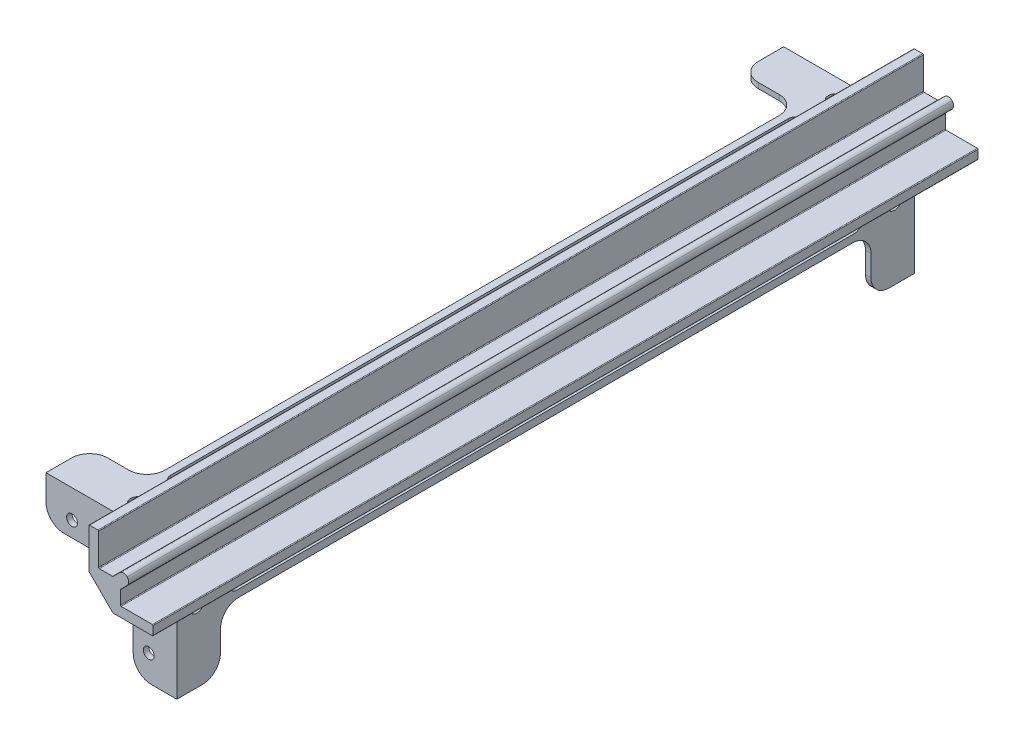
SolidWorks part; units mm, degrees
material "6061-T6 (SS)"
ref_plane "Front Plane" through (0, 0, 0) normal (0, 0, 1) x (1, 0, 0)
ref_plane "Top Plane" through (0, 0, 0) normal (0, 1, 0) x (1, 0, 0)
ref_plane "Right Plane" through (0, 0, 0) normal (1, 0, 0) x (0, 0, -1)
sketch "Sketch1" plane through (0, 0, 0) normal (0, 0, 1) x (1, 0, 0)
  line L0 (5.7105, 107.2306) -> (35.7105, 107.2306)
  line L5 (35.7105, 107.2306) -> (35.7105, 97.6946)
  line L8 (41.7105, 91.6946) -> (51.2465, 91.6946)
  line L9 (51.2465, 91.6946) -> (51.2465, 61.6946)
  line L26 (44.6218, 98.5558) -> (42.5718, 100.6058)
  line L36 (41.7105, 95.6446) -> (44.6218, 98.5558)
  line L37 (42.5718, 100.6058) -> (39.6605, 97.6946)
  line L38 (41.7105, 95.6446) -> (39.6605, 97.6946) construction
  line L39 (5.7105, 107.2306) -> (51.2465, 61.6946)
  line L46 (41.7105, 95.6446) -> (41.7105, 91.6946)
  line L47 (35.7105, 97.6946) -> (39.6605, 97.6946)
  point P44 (20.7124, 106.9061)
  dimension "D1" = 30
  dimension "D2" = 3.95
  dimension "D3" = 90
  dimension "D4" = 9.536
  dimension "D5" = 64.3976
extrude "Boss-Extrude1" add sketch "Sketch1" along normal blind 227
sketch "Sketch2" plane through (0, 0, 0) normal (0, 0, -1) x (-1, 0, 0)
  line L2 (-45.2465, 88.9946) -> (-45.2465, 80.9946)
  line L3 (-45.2465, 80.9946) -> (-43.7465, 80.9946)
  line L4 (-43.7465, 80.9946) -> (-43.7465, 88.9946)
  line L5 (-43.7465, 88.9946) -> (-39.6605, 88.9946)
  line L6 (-39.6605, 88.9946) -> (-33.0105, 95.6446)
  line L7 (-33.0105, 95.6446) -> (-33.0105, 99.7306)
  line L8 (-33.0105, 99.7306) -> (-25.0105, 99.7306)
  line L9 (-25.0105, 99.7306) -> (-25.0105, 101.2306)
  line L10 (-25.0105, 101.2306) -> (-33.0105, 101.2306)
  line L13 (27.2895, 108.6946) -> (-52.7105, 28.6946)
  line L16 (-51.2465, 61.6946) -> (-51.2465, 91.6946) construction
  line L17 (-35.7105, 107.2306) -> (-5.7105, 107.2306) construction
  line L19 (-52.7105, 92.6946) -> (-50.7105, 92.6946)
  line L20 (-50.7105, 92.6946) -> (-50.7105, 88.9946)
  line L21 (-50.7105, 88.9946) -> (-45.2465, 88.9946)
  line L22 (-52.7105, 92.6946) -> (-52.7105, 28.6946)
  line L23 (27.2895, 108.6946) -> (-36.7105, 108.6946)
  line L24 (-36.7105, 108.6946) -> (-36.7105, 106.6946)
  line L25 (-36.7105, 106.6946) -> (-33.0105, 106.6946)
  line L26 (-51.2465, 91.6946) -> (-41.7105, 91.6946) construction
  line L27 (-33.0105, 106.6946) -> (-33.0105, 101.2306)
  line L28 (-35.7105, 97.6946) -> (-35.7105, 107.2306) construction
  line L29 (-51.2465, 61.6946) -> (-51.2465, 91.6946) construction
  line L30 (-35.7105, 107.2306) -> (-5.7105, 107.2306) construction
  dimension "D2" = 2.7
  dimension "D3" = 2.7
  dimension "D4" = 64
  dimension "D5" = 1.5
  dimension "D6" = 8
  dimension "D7" = 1.5
  dimension "D8" = 8
  dimension "D9" = 6
  dimension "D10" = 6
  dimension "D11" = 0.536
  dimension "D12" = 0.536
  dimension "D13" = 2
  dimension "D14" = 2
  dimension "D15" = 1
  dimension "D16" = 1
extrude "Cut-Extrude1" cut sketch "Sketch2" against normal through all
sketch "Sketch3" plane through (0, 101.2306, 0) normal (0, 1, 0) x (1, 0, 0)
  line L1 (33.0105, -13.5) -> (23.0105, -13.5)
  line L2 (33.0105, -13.5) -> (33.0105, 2)
  line L3 (33.0105, 2) -> (23.0105, 2)
  line L4 (23.0105, -13.5) -> (23.0105, 2)
  line L5 (33.0105, -227) -> (25.0105, -227) construction
  line L6 (33.0105, -213.5) -> (23.0105, -213.5)
  line L7 (33.0105, -213.5) -> (33.0105, -229)
  line L8 (33.0105, -229) -> (23.0105, -229)
  line L9 (23.0105, -213.5) -> (23.0105, -229)
  line L14 (33.0105, 0) -> (25.0105, 0) construction
  line L15 (25.0105, -227) -> (25.0105, 0) construction
  line L16 (29.0105, -28.5) -> (29.0105, -198.5) construction
  line L17 (31.0105, -28.5) -> (31.0105, -198.5)
  line L18 (27.0105, -28.5) -> (27.0105, -198.5)
  arc A0 (31.0105, -28.5) -> (27.0105, -28.5) centre (29.0105, -28.5) ccw
  arc A1 (27.0105, -198.5) -> (31.0105, -198.5) centre (29.0105, -198.5) ccw
  point P22 (29.0105, -113.5)
  dimension "D8" = 2
  dimension "D1" = 13.5
  dimension "D2" = 13.5
  dimension "D3" = 2
  dimension "D4" = 15
  dimension "D6" = 2
  dimension "D7" = 2
  dimension "D9" = 4
  dimension "D10" = 15
extrude "Cut-Extrude2" cut sketch "Sketch3" against normal through all
sketch "Sketch4" plane through (45.2465, 0, 0) normal (1, 0, 0) x (0, 0, -1)
  line L1 (-213.5, 88.9946) -> (-229, 88.9946)
  line L2 (-213.5, 88.9946) -> (-213.5, 78.9946)
  line L3 (-213.5, 78.9946) -> (-229, 78.9946)
  line L4 (-229, 88.9946) -> (-229, 78.9946)
  line L5 (-227, 80.9946) -> (0, 80.9946) construction
  line L6 (-13.5, 88.9946) -> (2, 88.9946)
  line L7 (-13.5, 88.9946) -> (-13.5, 78.9946)
  line L8 (-13.5, 78.9946) -> (2, 78.9946)
  line L9 (2, 88.9946) -> (2, 78.9946)
  line L14 (0, 80.9946) -> (0, 88.9946) construction
  line L15 (-227, 80.9946) -> (-227, 88.9946) construction
  line L16 (-198.5, 84.9946) -> (-28.5, 84.9946) construction
  line L17 (-198.5, 86.9946) -> (-28.5, 86.9946)
  line L18 (-198.5, 82.9946) -> (-28.5, 82.9946)
  arc A0 (-198.5, 86.9946) -> (-198.5, 82.9946) centre (-198.5, 84.9946) ccw
  arc A1 (-28.5, 82.9946) -> (-28.5, 86.9946) centre (-28.5, 84.9946) ccw
  point P22 (-113.5, 84.9946)
  point P27 (-213.5, 83.9946)
  dimension "D9" = 2
  dimension "D1" = 2
  dimension "D2" = 2
  dimension "D3" = 2
  dimension "D4" = 13.5
  dimension "D5" = 13.5
  dimension "D6" = 2
  dimension "D7" = 15
  dimension "D8" = 4
  dimension "D10" = 15
extrude "Cut-Extrude3" cut sketch "Sketch4" against normal through all
fillet "Fillet3" radius 1.5 2 edges at (44.6218, 98.5558, 113.5) (42.5718, 100.6058, 113.5)
sketch "Sketch6" plane through (0, 0, 13.5) normal (0, 0, -1) x (-1, 0, 0)
  line L8 (-45.2465, 90.1946) -> (-45.2465, 65.2306)
  line L9 (-45.2465, 65.2306) -> (-33.2465, 65.2306)
  line L10 (-33.2465, 65.2306) -> (-33.2465, 89.2306)
  line L11 (-9.2465, 101.2306) -> (-34.2105, 101.2306)
  line L12 (-9.2465, 101.2306) -> (-9.2465, 89.2306)
  line L13 (-9.2465, 89.2306) -> (-33.2465, 89.2306)
  line L14 (-33.0105, 101.2306) -> (-25.0105, 101.2306) construction
  line L15 (-45.2465, 88.9946) -> (-45.2465, 80.9946) construction
  line L16 (-34.2105, 101.2306) -> (-34.2105, 96.2306)
  line L17 (-34.2105, 96.2306) -> (-40.2465, 90.1946)
  line L18 (-40.2465, 90.1946) -> (-45.2465, 90.1946)
  line L19 (-50.7105, 91.6946) -> (-41.7105, 91.6946) construction
  line L20 (-35.7105, 97.6946) -> (-35.7105, 106.6946) construction
  dimension "D1" = 12
  dimension "D2" = 24
  dimension "D3" = 1.5
  dimension "D4" = 1.5
  dimension "D5" = 5
extrude "Boss-Extrude3" add sketch "Sketch6" along normal blind 1.5
sketch "Sketch7" plane through (0, 0, 213.5) normal (0, 0, 1) x (1, 0, 0)
  line L0 (9.2465, 101.2306) -> (34.2105, 101.2306)
  line L1 (34.2105, 101.2306) -> (34.2105, 96.2306)
  line L2 (34.2105, 96.2306) -> (40.2465, 90.1946)
  line L3 (45.2465, 65.2306) -> (45.2465, 90.1946)
  line L4 (45.2465, 90.1946) -> (40.2465, 90.1946)
  line L5 (45.2465, 65.2306) -> (33.2465, 65.2306)
  line L6 (33.2465, 65.2306) -> (33.2465, 89.2306)
  line L7 (33.2465, 89.2306) -> (9.2465, 89.2306)
  line L8 (9.2465, 89.2306) -> (9.2465, 101.2306)
  line L9 (35.7105, 97.6946) -> (35.7105, 106.6946) construction
  line L10 (50.7105, 91.6946) -> (41.7105, 91.6946) construction
  dimension "D1" = 1.5
  dimension "D2" = 1.5
  dimension "D3" = 5
  dimension "D4" = 12
extrude "Boss-Extrude4" add sketch "Sketch7" along normal blind 1.5
sketch "Sketch9" plane through (0, 101.2306, 0) normal (0, 1, 0) x (1, 0, 0)
  line L0 (35.2465, -215) -> (9.2465, -215)
  line L1 (9.2465, -215) -> (9.2465, -203)
  line L2 (9.2465, -203) -> (35.2465, -203)
  line L3 (35.2465, -203) -> (35.2465, -215)
  line L4 (35.2465, -12) -> (9.2465, -12)
  line L5 (9.2465, -12) -> (9.2465, -24)
  line L6 (9.2465, -24) -> (35.2465, -24)
  line L7 (35.2465, -24) -> (35.2465, -12)
  dimension "D1" = 12
  dimension "D2" = 26
extrude "Boss-Extrude5" add sketch "Sketch9" against normal blind 1.5
sketch "Sketch10" plane through (45.2465, 0, 0) normal (1, 0, 0) x (0, 0, -1)
  line L0 (-215, 65.2306) -> (-215, 91.2306)
  line L1 (-215, 91.2306) -> (-203, 91.2306)
  line L2 (-203, 91.2306) -> (-203, 65.2306)
  line L3 (-203, 65.2306) -> (-215, 65.2306)
  line L4 (-12, 65.2306) -> (-12, 91.2306)
  line L5 (-12, 91.2306) -> (-24, 91.2306)
  line L6 (-24, 91.2306) -> (-24, 65.2306)
  line L7 (-24, 65.2306) -> (-12, 65.2306)
  dimension "D1" = 12
  dimension "D2" = 26
extrude "Boss-Extrude6" add sketch "Sketch10" against normal blind 1.5
fillet "Fillet7" radius 5 14 edges at (9.2465, 100.4806, 24) (9.2465, 89.2306, 12.75) (33.2465, 89.2306, 12.75) (33.2465, 65.2306, 12.75) (44.4965, 65.2306, 24) (44.4965, 80.9946, 24) (25.0105, 100.4806, 24) (44.4965, 80.9946, 203) (25.0105, 100.4806, 203) (9.2465, 100.4806, 203) (44.4965, 65.2306, 203) (33.2465, 65.2306, 214.25) (9.2465, 89.2306, 214.25) (33.2465, 89.2306, 214.25)
sketch "Sketch11" plane through (45.2465, 0, 0) normal (1, 0, 0) x (0, 0, -1)
  line L1 (-215, 65.2306) -> (-215, 88.9946) construction
  line L3 (-12, 88.9946) -> (-12, 65.2306) construction
  line L4 (-227, 88.9946) -> (0, 88.9946) construction
  circle A0 centre (-209.5, 84.9946) radius 2
  circle A1 centre (-17.5, 84.9946) radius 2
  dimension "D1" = 4
  dimension "D6" = 4
  dimension "D2" = 4
  dimension "D3" = 5.5
  dimension "D4" = 4
  dimension "D5" = 5.5
extrude "Cut-Extrude4" cut sketch "Sketch11" against normal blind 10
sketch "Sketch12" plane through (0, 101.2306, 0) normal (0, 1, 0) x (1, 0, 0)
  line L1 (9.2465, -12) -> (33.0105, -12) construction
  line L2 (33.0105, -215) -> (9.2465, -215) construction
  line L3 (33.0105, -227) -> (33.0105, 0) construction
  circle A0 centre (29.0105, -17.5) radius 2
  circle A1 centre (29.0105, -209.5) radius 2
  dimension "D1" = 4
  dimension "D6" = 4
  dimension "D2" = 4
  dimension "D3" = 5.5
  dimension "D4" = 5.5
  dimension "D5" = 4
extrude "Cut-Extrude5" cut sketch "Sketch12" against normal blind 10
fillet "Fillet8" radius 0.2 8 edges at (41.7105, 95.6446, 113.5) (39.6605, 97.6946, 113.5) (50.7105, 91.6946, 113.5) (41.7105, 91.6946, 113.5) (35.7105, 97.6946, 113.5) (35.7105, 106.6946, 113.5) (50.7105, 88.9946, 113.5) (33.0105, 106.6946, 113.5)
hole_wizard "Ø3.0mm Dowel Hole1" positions "Sketch13" profile "Sketch14" hole size "Ø3.0" standard "ANSI Metric" end condition through all
sketch "Sketch13" plane through (0, 0, 215) normal (0, 0, 1) x (1, 0, 0)
  line L0 (16.4105, 93.4946) -> (16.4105, 89.2306) construction
  line L1 (14.2465, 89.2306) -> (28.2465, 89.2306) construction
  line L3 (9.2465, 101.2306) -> (9.2465, 94.2306) construction
  point P0 (16.4105, 93.4946)
  dimension "D1" = 7.164
  dimension "D2" = 4.264
sketch "Sketch14" plane through (16.4105, 93.4946, 215) normal (1, 0, 0) x (0, -1, 0)
  line L0 (0, 0) -> (0, 215)
  line L1 (0, 215) -> (1.5, 215)
  line L2 (1.5, 215) -> (1.5, 0)
  line L5 (1.5, 0) -> (0, 0)
  line L11 (0, -6.35) -> (0, 107.95) construction
  dimension "Thru Hole Dia." = 3
  dimension "Thru Hole Depth" = 215
hole_wizard "Ø3.0mm Dowel Hole2" positions "Sketch15" profile "Sketch16" hole size "Ø3.0" standard "ANSI Metric" end condition through all
sketch "Sketch15" plane through (0, 0, 215) normal (0, 0, 1) x (1, 0, 0)
  line L0 (33.2465, 72.3946) -> (37.5105, 72.3946) construction
  line L1 (33.2465, 84.2306) -> (33.2465, 70.2306) construction
  line L3 (38.2465, 65.2306) -> (45.2465, 65.2306) construction
  point P0 (37.5105, 72.3946)
  dimension "D1" = 7.164
  dimension "D2" = 4.264
sketch "Sketch16" plane through (37.5105, 72.3946, 215) normal (1, 0, 0) x (0, -1, 0)
  line L0 (0, 0) -> (0, 215)
  line L1 (0, 215) -> (1.5, 215)
  line L2 (1.5, 215) -> (1.5, 0)
  line L5 (1.5, 0) -> (0, 0)
  line L11 (0, -6.35) -> (0, 107.95) construction
  dimension "Thru Hole Dia." = 3
  dimension "Thru Hole Depth" = 215
